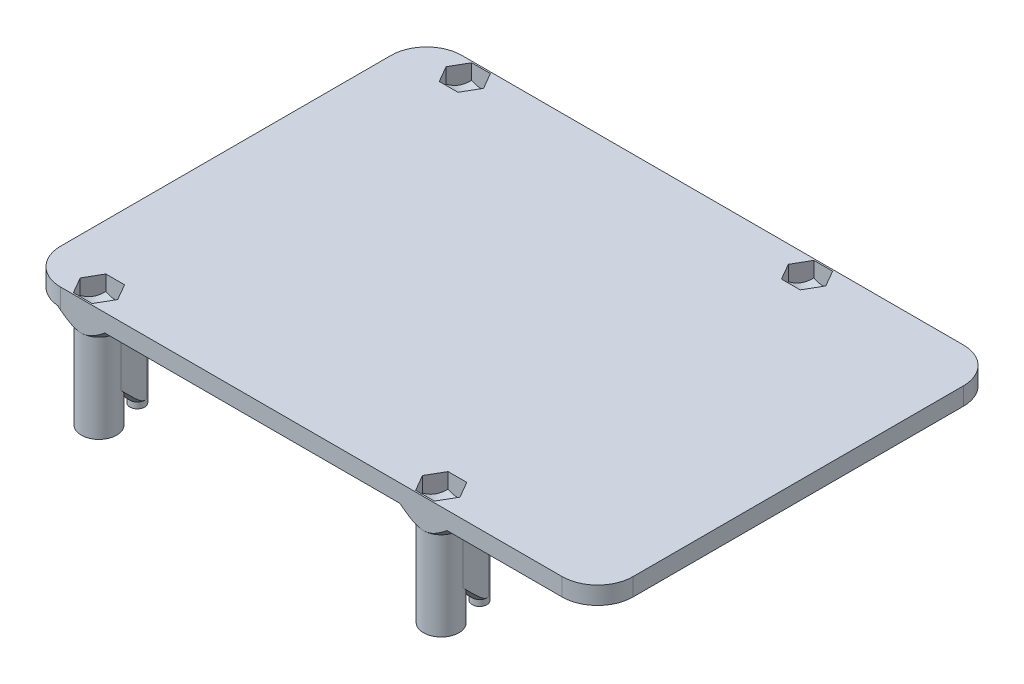
SolidWorks part; units mm, degrees
ref_plane "Front Plane" through (0, 0, 0) normal (0, 0, 1) x (1, 0, 0)
ref_plane "Top Plane" through (0, 0, 0) normal (0, 1, 0) x (1, 0, 0)
ref_plane "Right Plane" through (0, 0, 0) normal (1, 0, 0) x (0, 0, -1)
sketch "Sketch1" plane through (0, 0, 0) normal (0, 1, 0) x (1, 0, 0)
  line L0 (9.9631, -5.1238) -> (9.9631, -11.1238) construction
  line L1 (-34.1949, -5.1238) -> (50.8051, -5.1238) construction
  line L2 (-34.1949, -5.1238) -> (-34.1949, 50.8762) construction
  line L3 (-34.1949, 50.8762) -> (50.8051, 50.8762) construction
  line L4 (50.8051, -5.1238) -> (50.8051, 50.8762) construction
  line L9 (-34.1949, -11.1238) -> (50.8051, -11.1238)
  line L10 (-40.1949, -5.1238) -> (-40.1949, 50.8762)
  line L11 (-34.1949, 56.8762) -> (50.8051, 56.8762)
  line L12 (56.8051, -5.1238) -> (56.8051, 50.8762)
  line L13 (19.9822, 50.8762) -> (19.9822, 56.8762) construction
  line L14 (50.8051, 10.62) -> (56.8051, 10.62) construction
  line L15 (-34.1949, 12.5958) -> (-40.1949, 12.5958) construction
  line L16 (-30.6949, -1.6238) -> (-30.6949, -5.1238) construction
  line L17 (-30.6949, -1.6238) -> (-34.1949, -1.6238) construction
  line L18 (-33.5842, -7.3161) -> (-31.8988, -1.2873)
  line L19 (24.4158, -7.3161) -> (26.1012, -1.2873)
  line L20 (-30.6949, -1.6238) -> (-30.6949, -5.1238) construction
  line L21 (-30.6949, 47.3762) -> (-34.1949, 47.3762) construction
  line L22 (-30.6949, 47.3762) -> (-30.6949, 50.8762) construction
  line L23 (-27.8057, -7.3161) -> (-29.4911, -1.2873)
  line L24 (30.1943, -7.3161) -> (28.5089, -1.2873)
  line L25 (28.5089, 47.0396) -> (30.1943, 53.0685)
  line L26 (24.4158, 53.0685) -> (26.1012, 47.0396)
  line L27 (-29.4911, 47.0396) -> (-27.8057, 53.0685)
  line L28 (-31.8988, 47.0396) -> (-33.5842, 53.0685)
  circle A4 centre (27.3051, -8.1238) radius 1.75
  circle A5 centre (27.3051, 53.8762) radius 1.75
  circle A6 centre (-30.6949, 53.8762) radius 1.75
  circle A7 centre (-30.6949, -8.1238) radius 1.75
  circle A8 centre (-30.6949, -1.6238) radius 1.25
  circle A9 centre (-30.6949, 47.3762) radius 1.25
  circle A10 centre (27.3051, -1.6238) radius 1.25
  circle A11 centre (27.3051, 47.3762) radius 1.25
  circle A12 centre (27.3051, 53.8762) radius 3
  circle A13 centre (27.3051, -8.1238) radius 3
  circle A14 centre (-30.6949, -8.1238) radius 3
  circle A15 centre (-30.6949, 53.8762) radius 3
  arc A16 (50.8051, 56.8762) -> (56.8051, 50.8762) centre (50.8051, 50.8762) cw
  arc A17 (50.8051, -11.1238) -> (56.8051, -5.1238) centre (50.8051, -5.1238) ccw
  arc A18 (-40.1949, 50.8762) -> (-34.1949, 56.8762) centre (-34.1949, 50.8762) cw
  arc A19 (-34.1949, -11.1238) -> (-40.1949, -5.1238) centre (-34.1949, -5.1238) cw
  dimension "D7" = 3.5
  dimension "D5" = 2.5
  dimension "D12" = 6
  dimension "D13" = 6
  dimension "D9" = 6.26
  dimension "D2" = 49
  dimension "D3" = 58
  dimension "D4" = 3.5
  dimension "D6" = 85
  dimension "D8" = 3
  dimension "D10" = 6
  dimension "D11" = 3
extrude "base" add sketch "Sketch1" along normal blind 3 contours L9 A17 L12 A16 L11 A18 L10 A19
extrude "m3_holes" cut sketch "Sketch1<7>" along normal through all contours A7 | A4 | A5 | A6 region at (27.3051, 0, 8.1238) region at (27.3051, 0, -53.8762) region at (-30.6949, 0, -53.8762) region at (-30.6949, 0, 8.1238)
sketch "Sketch1<7>" plane through (0, 0, 0) normal (0, 1, 0) x (1, 0, 0) same geometry as "Sketch1"
extrude "bosses" add sketch "Sketch1<3>" against normal blind 9 contours A9 | A14 L23 A8 L18 | A8 | A14 A7 | A13 A4 | A10 | A13 L24 A10 L19 | A12 L26 A11 L25 | A11 | A12 A5 | A15 A6 | A15 L28 A9 L27
sketch "Sketch1<3>" plane through (0, 0, 0) normal (0, 1, 0) x (1, 0, 0) same geometry as "Sketch1"
extrude "interface" add sketch "Sketch1<6>" against normal blind 8 from surface contours A14 A7 | A8 | A13 A4 | A10 | A11 | A12 A5 | A9 | A15 A6 region at (-33.0172, 0, 9.8859) region at (24.9828, 0, 9.8859) region at (29.3664, 0, -55.9375) region at (-28.6336, 0, -55.9375) region at (-30.6949, 0, 1.6238) region at (27.3051, 0, 1.6238) region at (-30.6949, 0, -47.3762) region at (27.3051, 0, -47.3762) starting at face at (-30.6949, -9, -50.7776)
sketch "Sketch1<6>" plane through (0, 0, 0) normal (0, 1, 0) x (1, 0, 0) same geometry as "Sketch1"
sketch "Sketch7" plane through (0, 3, 0) normal (0, 1, 0) x (1, 0, 0)
  line L1 (-29.1072, 51.1262) -> (-27.5195, 53.8762)
  line L2 (-27.5195, 53.8762) -> (-29.1072, 56.6262)
  line L3 (-29.1072, 56.6262) -> (-32.2827, 56.6262)
  line L4 (-32.2827, 56.6262) -> (-33.8704, 53.8762)
  line L5 (-33.8704, 53.8762) -> (-32.2827, 51.1262)
  line L6 (-32.2827, 51.1262) -> (-29.1072, 51.1262)
  line L7 (28.8928, 51.1262) -> (30.4805, 53.8762)
  line L8 (30.4805, 53.8762) -> (28.8928, 56.6262)
  line L9 (28.8928, 56.6262) -> (25.7173, 56.6262)
  line L10 (25.7173, 56.6262) -> (24.1296, 53.8762)
  line L11 (24.1296, 53.8762) -> (25.7173, 51.1262)
  line L12 (25.7173, 51.1262) -> (28.8928, 51.1262)
  line L13 (25.7173, -10.8738) -> (28.8928, -10.8738)
  line L14 (28.8928, -10.8738) -> (30.4805, -8.1238)
  line L15 (30.4805, -8.1238) -> (28.8928, -5.3738)
  line L16 (28.8928, -5.3738) -> (25.7173, -5.3738)
  line L17 (25.7173, -5.3738) -> (24.1296, -8.1238)
  line L18 (24.1296, -8.1238) -> (25.7173, -10.8738)
  line L19 (-32.2827, -10.8738) -> (-29.1072, -10.8738)
  line L20 (-29.1072, -10.8738) -> (-27.5195, -8.1238)
  line L21 (-27.5195, -8.1238) -> (-29.1072, -5.3738)
  line L22 (-29.1072, -5.3738) -> (-32.2827, -5.3738)
  line L23 (-32.2827, -5.3738) -> (-33.8704, -8.1238)
  line L24 (-33.8704, -8.1238) -> (-32.2827, -10.8738)
  circle A0 centre (-30.6949, 53.8762) radius 2.75 construction
  circle A1 centre (27.3051, 53.8762) radius 2.75 construction
  circle A2 centre (27.3051, -8.1238) radius 2.75 construction
  circle A3 centre (-30.6949, -8.1238) radius 2.75 construction
  dimension "D1" = 5.5
extrude "Cut-Extrude6" cut sketch "Sketch7" against normal blind 2
chamfer "Chamfer1" distance 2 angle 45 4 edges at (-30.6949, 1, -52.1262) (-30.6949, 1, 9.8738) (27.3051, 1, 9.8738) (27.3051, 1, -52.1262)
chamfer "Chamfer3" distance 2 angle 45 19 edges at (-30.6949, 0, -46.1262) (-32.7415, 0, -50.0541) (-28.6484, 0, -50.0541) (-33.0848, 0, -55.6896) (-28.3051, 0, -55.6896) (27.3051, 0, 0.3738) (29.3516, 0, 4.3017) (25.2585, 0, 4.3017) (29.6949, 0, 9.9372) (24.9152, 0, 9.9372) (27.3051, 0, -46.1262) (25.2585, 0, -50.0541) (29.3516, 0, -50.0541) (24.9152, 0, -55.6896) (29.6949, 0, -55.6896) (-32.7415, 0, 4.3017) (-30.6949, 0, 0.3738) (-28.6484, 0, 4.3017) (-28.3051, 0, 9.9372)
chamfer "Chamfer4" distance 7 angle 45 4 edges at (27.3051, -9, 2.8738) (27.3051, -9, -48.6262) (-30.6949, -9, -48.6262) (-30.6949, -9, 2.8738)
